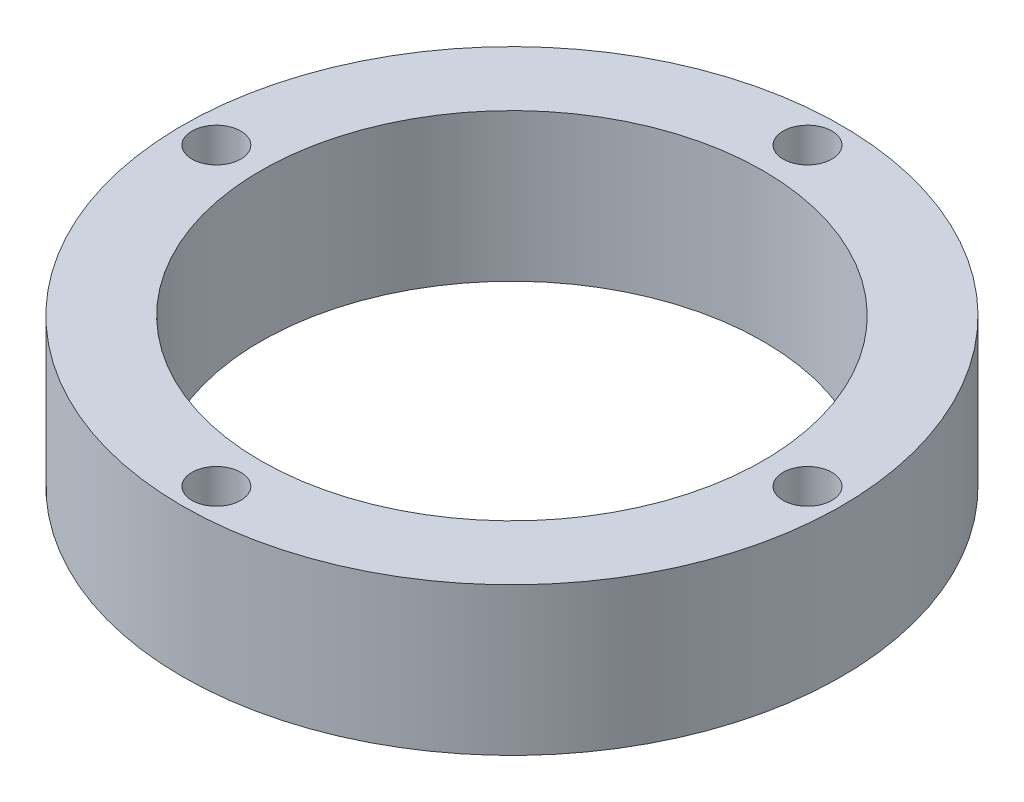
SolidWorks part; units mm, degrees
ref_plane "Front" through (0, 0, 0) normal (0, 0, 1) x (1, 0, 0)
ref_plane "Top" through (0, 0, 0) normal (0, 1, 0) x (1, 0, 0)
ref_plane "Right" through (0, 0, 0) normal (1, 0, 0) x (0, 0, -1)
sketch "Sketch1" plane through (0, 0, 0) normal (0, 1, 0) x (1, 0, 0)
  circle A0 centre (0, 0) radius 17
  circle A1 centre (0, 0) radius 22.3005
extrude "Boss-Extrude1" add sketch "Sketch1" along normal blind 10
sketch "Sketch2" plane through (0, 10, 0) normal (0, 1, 0) x (1, 0, 0)
  line L0 (0, 0) -> (0, 20)
  circle A0 centre (0, 20) radius 1.65
  circle A1 centre (20, 0) radius 1.65
  circle A2 centre (0, -20) radius 1.65
  circle A3 centre (-20, 0) radius 1.65
  point P13 (0, 0)
  dimension "D2" = 4
  dimension "D1" = 20
extrude "Cut-Extrude1" cut sketch "Sketch2" against normal through all contours A0 | A1 | A2 | A3 region at (1.1337, 10, -18.8663) region at (20, 10, 0) region at (0, 10, 20)
